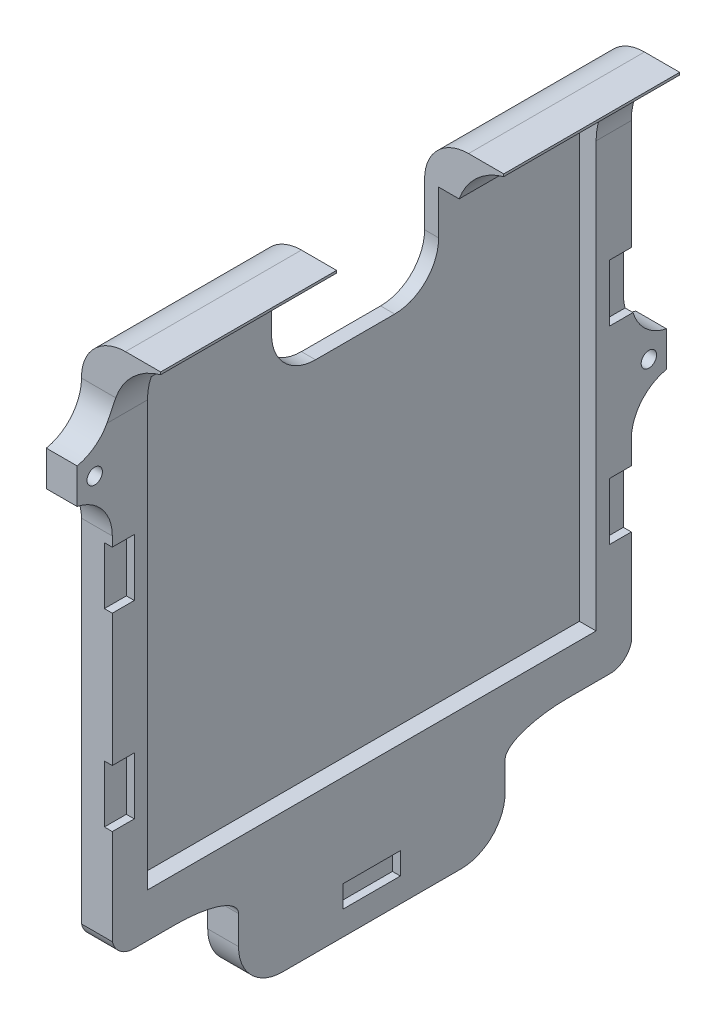
SolidWorks part; units mm, degrees
ref_plane "Front Plane" through (0, 0, 0) normal (0, 0, 1) x (1, 0, 0)
ref_plane "Top Plane" through (0, 0, 0) normal (0, 1, 0) x (1, 0, 0)
ref_plane "Right Plane" through (0, 0, 0) normal (1, 0, 0) x (0, 0, -1)
sketch "Sketch1" plane through (0, 0, 0) normal (0, 0, 1) x (1, 0, 0)
  line L0 (3.4895, 72.6316) -> (3.4895, 65.6316)
  line L1 (-28.7105, -72.8684) -> (-21.7105, -72.8684)
  line L2 (-28.7105, -72.8684) -> (-28.7105, 57.6316)
  line L4 (-21.7105, -72.8684) -> (-21.7105, 50.6316)
  line L5 (-13.7105, 72.6316) -> (3.4895, 72.6316)
  line L6 (-30.2105, 77.6316) -> (-30.2105, 72.6316)
  line L7 (-6.7105, 65.6316) -> (3.4895, 65.6316)
  arc A0 (-28.7105, 57.6316) -> (-13.7105, 72.6316) centre (-13.7105, 57.6316) cw
  arc A1 (-6.7105, 65.6316) -> (-21.7105, 50.6316) centre (-6.7105, 50.6316) ccw
  dimension "D1" = 15
  dimension "D2" = 15
  dimension "D3" = 130.5
  dimension "D4" = 15
  dimension "D5" = 7
  dimension "D6" = 17.2
  dimension "D7" = 7
  dimension "D8" = 8
extrude "Boss-Extrude1" add sketch "Sketch1" along normal blind 118 contours A1 L7 L0 L5 A0 L2 | L1 L4 L2 region at (-22.5509, 9.8219, 0)
sketch "Sketch2" plane through (0, 72.6316, 0) normal (0, 1, 0) x (1, 0, 0)
  line L0 (-13.7105, 0) -> (3.4895, 0) construction
  line L1 (-0.0105, -24) -> (-9.0105, -24)
  line L2 (-0.0105, -24) -> (-0.0105, -39)
  line L3 (-0.0105, -39) -> (-9.0105, -39)
  line L4 (-9.0105, -24) -> (-9.0105, -39)
  line L5 (3.4895, -118) -> (3.4895, 0) construction
  dimension "D1" = 24
  dimension "D2" = 9
  dimension "D3" = 15
  dimension "D4" = 3.5
ref_plane "Plane1" through (0, 0, 59) normal (0, 0, 1) x (1, 0, 0)
extrude "Cut-Extrude2" cut sketch "Sketch2" against normal up to surface (7 mm away) up to face at (-1.6105, 65.6316, 59)
sketch "Sketch5" plane through (-28.7105, 0, 0) normal (-1, 0, 0) x (0, 0, 1)
  line L0 (6, -67.9143) -> (6, 95.8293)
  line L1 (0, -72.8684) -> (0, 50.6316) construction
  line L3 (6, 95.8293) -> (135.0936, 95.8293)
  line L4 (6, 95.8293) -> (6, -67.9143)
  line L5 (6, -67.9143) -> (135.0936, -67.9143)
  line L6 (135.0936, 95.8293) -> (135.0936, -67.9143)
  line M7 (0, -72.8684) -> (118, -72.8684)
  line M8 (118, -72.8684) -> (118, 57.6316)
  line M9 (118, 57.6316) -> (0, 57.6316)
  dimension "D1" = 6
extrude "Cut-Extrude3" [suppressed] cut sketch "Sketch5" against normal blind 98 contours L0 M7 M8 M9 | L6 L3 L0 L5 M9 M8 M7
sketch "Sketch6" plane through (3.4895, 0, 0) normal (1, 0, 0) x (0, 0, -1)
  line L0 (0, 72.6316) -> (0, 65.6316) construction
  line L1 (-21.84, 75.0007) -> (-8.84, 75.0007)
  line L2 (-21.84, 75.0007) -> (-21.84, 67.2604)
  line L3 (-21.84, 67.2604) -> (-8.84, 67.2604)
  line L4 (-8.84, 75.0007) -> (-8.84, 67.2604)
  dimension "D1" = 8.84
  dimension "D2" = 13
extrude "Cut-Extrude4" cut sketch "Sketch6" against normal blind 1.8
sketch "Sketch8" plane through (0, 0, 0) normal (0, 0, -1) x (-1, 0, 0)
  line L0 (21.7105, -72.8684) -> (21.7105, 50.6316) construction
  line L1 (21.7105, 25.6316) -> (23.5105, 25.6316)
  line L2 (21.7105, 25.6316) -> (21.7105, 12.6316)
  line L3 (21.7105, 12.6316) -> (23.5105, 12.6316)
  line L4 (23.5105, 25.6316) -> (23.5105, 12.6316)
  line L5 (13.7105, 72.6316) -> (-3.4895, 72.6316) construction
  line L6 (21.7105, -17.3684) -> (23.5105, -17.3684)
  line L7 (21.7105, -17.3684) -> (21.7105, -30.3684)
  line L8 (21.7105, -30.3684) -> (23.5105, -30.3684)
  line L9 (23.5105, -17.3684) -> (23.5105, -30.3684)
  dimension "D1" = 1.8
  dimension "D2" = 47
  dimension "D3" = 13
  dimension "D4" = 13
  dimension "D5" = 30
  dimension "D6" = 1.8
extrude "Cut-Extrude5" cut sketch "Sketch8" against normal blind 5
mirror "Mirror1" about plane through (0, 0, 59) normal (0, 0, 1) of "Cut-Extrude5"
sketch "Sketch9" plane through (0, 0, 118) normal (0, 0, 1) x (1, 0, 0)
  line L1 (3.4895, 65.6316) -> (-9.5105, 65.6316)
  line L2 (3.4895, 65.6316) -> (3.4895, 67.4316)
  line L3 (3.4895, 67.4316) -> (-9.5105, 67.4316)
  line L4 (-9.5105, 65.6316) -> (-9.5105, 67.4316)
  dimension "D1" = 1.8
  dimension "D2" = 13
extrude "Cut-Extrude6" cut sketch "Sketch9" against normal blind 5
sketch "Sketch11" [suppressed] plane through (-28.7105, 0, 0) normal (-1, 0, 0) x (0, 0, 1)
  line L0 (0, -35.8684) -> (0, -72.3684)
  line L1 (0, -72.3684) -> (39, -72.3684)
  line L2 (118, -72.3684) -> (118, -26.8684)
  line L3 (79, -72.3684) -> (118, -72.3684)
  line L20 (13, -29.8684) -> (8, -29.8684)
  line L21 (5, -26.8684) -> (0, -26.8684)
  line L22 (0, -26.8684) -> (0, -35.8684)
  line L23 (0, -35.8684) -> (14.4398, -35.8684)
  line L24 (31.6067, -45.8684) -> (31.6067, -50.8684)
  line L25 (31.6067, -50.8684) -> (39, -50.8684)
  line L26 (39, -50.8684) -> (39, -62.8684)
  line L27 (44, -67.8684) -> (74, -67.8684)
  line L28 (79, -62.8684) -> (79, -50.8684)
  line L29 (79, -50.8684) -> (86.3933, -50.8684)
  line L30 (86.3933, -50.8684) -> (86.3933, -45.8684)
  line L31 (103.5602, -35.8684) -> (118, -35.8684)
  line L32 (118, -35.8684) -> (118, -26.8684)
  line L33 (118, -26.8684) -> (113, -26.8684)
  line L34 (13, -29.8684) -> (8, -29.8684)
  line L35 (110, -29.8684) -> (62, -29.8684)
  line L36 (57, -24.8684) -> (57, -17.8684)
  line L37 (57, -17.8684) -> (18, -17.8684)
  line L38 (18, -17.8684) -> (18, -24.8684)
  line L39 (110, -29.8684) -> (62, -29.8684)
  line L42 (0, -26.8684) -> (0, -35.8684)
  line L43 (0, -35.8684) -> (14.4398, -35.8684)
  line L44 (31.6067, -45.8684) -> (31.6067, -50.8684)
  line L45 (31.6067, -50.8684) -> (39, -50.8684)
  line L46 (39, -50.8684) -> (39, -72.3684)
  line L48 (79, -72.3684) -> (79, -50.8684)
  line L49 (79, -50.8684) -> (86.3933, -50.8684)
  line L50 (86.3933, -50.8684) -> (86.3933, -45.8684)
  line L51 (103.5602, -35.8684) -> (118, -35.8684)
  line L52 (118, -35.8684) -> (118, -26.8684)
  arc A8 (5, -26.8684) -> (8, -29.8684) centre (8, -26.8684) ccw
  arc A9 (5, -26.8684) -> (8, -29.8684) centre (8, -26.8684) ccw
  arc A10 (110, -29.8684) -> (113, -26.8684) centre (110, -26.8684) ccw
  arc A11 (110, -29.8684) -> (113, -26.8684) centre (110, -26.8684) ccw
  arc A12 (57, -24.8684) -> (62, -29.8684) centre (62, -24.8684) ccw
  arc A13 (57, -24.8684) -> (62, -29.8684) centre (62, -24.8684) ccw
  arc A14 (13, -29.8684) -> (18, -24.8684) centre (13, -24.8684) ccw
  arc A15 (13, -29.8684) -> (18, -24.8684) centre (13, -24.8684) ccw
  arc A24 (74, -67.8684) -> (79, -62.8684) centre (74, -62.8684) ccw
  arc A25 (74, -67.8684) -> (79, -62.8684) centre (74, -62.8684) ccw
  arc A26 (39, -62.8684) -> (44, -67.8684) centre (44, -62.8684) ccw
  arc A27 (39, -62.8684) -> (44, -67.8684) centre (44, -62.8684) ccw
  ellipse E2 centre (14.4398, -45.8684) end of major axis (31.6067, -45.8684) minor radius 10 (31.6067, -45.8684) -> (14.4398, -35.8684) ccw
  ellipse E3 centre (103.5602, -45.8684) end of major axis (86.3933, -45.8684) minor radius 10 (103.5602, -35.8684) -> (86.3933, -45.8684) ccw
  ellipse E4 centre (14.4398, -45.8684) end of major axis (31.6067, -45.8684) minor radius 10 (31.6067, -45.8684) -> (14.4398, -35.8684) ccw
  ellipse E5 centre (103.5602, -45.8684) end of major axis (86.3933, -45.8684) minor radius 10 (103.5602, -35.8684) -> (86.3933, -45.8684) ccw
  dimension "D1" = 0
sketch "Sketch14" plane through (-21.7105, 0, 0) normal (1, 0, 0) x (0, 0, -1)
  line L12 (-85.5934, -0.8635) -> (-45.5934, -0.8635)
  line L13 (-83.0934, 1.6365) -> (-48.0934, 1.6365)
  line L15 (-83.0934, 1.6365) -> (-83.0934, 51.6365)
  line L17 (-48.0934, 1.6365) -> (-48.0934, 51.6365)
  line L18 (-45.5934, -0.8635) -> (-45.5934, 51.6365)
  line L20 (-85.5934, -0.8635) -> (-85.5934, 51.6365)
  line L21 (-85.5934, 51.6365) -> (-83.0934, 51.6365)
  line L23 (-85.5934, -0.8635) -> (-85.5934, 54.1365) construction
  line L24 (-85.5934, 54.1365) -> (-45.5934, 54.1365) construction
  line L25 (-45.5934, -0.8635) -> (-45.5934, 54.1365) construction
  line L26 (-83.0934, 51.6365) -> (-48.0934, 51.6365) construction
  line L27 (-48.0934, 51.6365) -> (-45.5934, 51.6365)
  dimension "D1" = 2.5
  dimension "D2" = 35
  dimension "D3" = 50
extrude "Boss-Extrude3" [suppressed] add sketch "Sketch14" along normal blind 10
sketch "Sketch15" plane through (3.4895, 0, 0) normal (1, 0, 0) x (0, 0, -1)
  line L0 (-113, 65.6316) -> (0, 65.6316) construction
  line L1 (-118, 65.6316) -> (0, 65.6316)
  line L2 (-118, 65.6316) -> (-118, 72.6316)
  line L3 (-118, 72.6316) -> (0, 72.6316)
  line L4 (0, 65.6316) -> (0, 72.6316)
  dimension "D1" = 0
extrude "Cut-Extrude7" cut sketch "Sketch15" against normal blind 57
sketch "Sketch24" plane through (-28.7105, 0, 0) normal (-1, 0, 0) x (0, 0, 1)
  line L0 (5, -44.8684) -> (5, 52.9406)
  line L1 (5, 52.9406) -> (0, 52.9406)
  line L2 (0, 52.9406) -> (0, -52.0594)
  line L3 (31.6067, -72.8684) -> (31.6067, -67.8684)
  line L4 (28.6941, -60.8684) -> (28.6941, -67.8684)
  line L5 (31.6067, -67.8684) -> (31.6067, -60.8684)
  line L6 (5, -55.8684) -> (14.4398, -55.8684)
  line L7 (14.4398, -50.8684) -> (11, -50.8684)
  line L8 (0, -72.8684) -> (0, 57.6316) construction
  line L9 (118, -72.8684) -> (0, -72.8684) construction
  line L47 (59, 91.3004) -> (59, -88.244) construction
  line L48 (59, -17.71) -> (59, 17.71) construction
  line L49 (103.5602, -50.8684) -> (107, -50.8684)
  line L50 (113, -55.8684) -> (103.5602, -55.8684)
  line L51 (86.3933, -67.8684) -> (86.3933, -60.8684)
  line L52 (89.3059, -60.8684) -> (89.3059, -67.8684)
  line L53 (86.3933, -72.8684) -> (86.3933, -67.8684)
  line L54 (118, 52.9406) -> (118, -52.0594)
  line L55 (113, 52.9406) -> (118, 52.9406)
  line L56 (113, -44.8684) -> (113, 52.9406)
  line L57 (31.6067, -72.8684) -> (86.3933, -72.8684)
  line L58 (0, -52.0594) -> (0, -72.8684)
  line L59 (0, -72.8684) -> (31.6067, -72.8684)
  line L60 (86.3933, -72.8684) -> (118, -72.8684)
  line L61 (118, -72.8684) -> (118, -52.0594)
  arc A0 (5, -44.8684) -> (11, -50.8684) centre (11, -44.8684) ccw
  arc A1 (0, -52.0594) -> (5, -55.8684) centre (4.8566, -50.8705) ccw
  arc A8 (118, -52.0594) -> (113, -55.8684) centre (113.1434, -50.8705) cw
  arc A9 (113, -44.8684) -> (107, -50.8684) centre (107, -44.8684) cw
  ellipse E0 centre (31.6067, -67.8684) end of major axis (31.6067, -62.8684) minor radius 2.9126 (28.6941, -67.8684) -> (31.6067, -72.8684) ccw
  ellipse E1 centre (14.4398, -60.8684) end of major axis (28.6941, -60.8684) minor radius 5 (28.6941, -60.8684) -> (14.4398, -55.8684) ccw
  ellipse E2 centre (14.4398, -60.8684) end of major axis (31.6067, -60.8684) minor radius 10 (31.6067, -60.8684) -> (14.4398, -50.8684) ccw
  ellipse E3 centre (103.5602, -60.8684) end of major axis (86.3933, -60.8684) minor radius 10 (86.3933, -60.8684) -> (103.5602, -50.8684) cw
  ellipse E4 centre (103.5602, -60.8684) end of major axis (117.8144, -60.8684) minor radius 5 (89.3059, -60.8684) -> (103.5602, -55.8684) cw
  ellipse E5 centre (86.3933, -67.8684) end of major axis (86.3933, -62.8684) minor radius 2.9126 (89.3059, -67.8684) -> (86.3933, -72.8684) cw
  line M56 (0, 57.6316) -> (0, -72.8684)
  line M57 (0, -72.8684) -> (118, -72.8684)
  line M58 (118, -72.8684) -> (118, 57.6316)
  dimension "D1" = 0
  dimension "D2" = 0
extrude "Cut-Extrude8" cut sketch "Sketch24" against normal blind 57 contours L4 E1 L6 A1 E0 M56 M57 | L52 E5 A8 L50 E4 M57 M58 region at (-28.7105, -64.5576, 104.0418) region at (-28.7105, -64.5576, 13.9582)
fillet "Fillet1" radius 10 1 edges at (-26.3991, 65.6316, 59)
sketch "Sketch26" plane through (-28.7105, 0, 0) normal (-1, 0, 0) x (0, 0, 1)
  line L0 (0, -52.0594) -> (0, 55.6316) construction
  line L1 (0, 5.6316) -> (-8, 5.6316)
  line L2 (0, 5.6316) -> (0, -2.3684)
  line L3 (0, -2.3684) -> (-8, -2.3684)
  line L4 (-8, 5.6316) -> (-8, -2.3684)
  line L5 (118, -52.0594) -> (118, 55.6316) construction
  line L6 (118, 45.6316) -> (126, 45.6316)
  line L7 (118, 45.6316) -> (118, 37.6316)
  line L8 (118, 37.6316) -> (126, 37.6316)
  line L9 (126, 45.6316) -> (126, 37.6316)
  line L10 (0, 65.6316) -> (118, 65.6316) construction
  circle A0 centre (122, 41.6316) radius 1.75
  circle A1 centre (-4, 1.6316) radius 1.75
  dimension "D7" = 3.5
  dimension "D8" = 4
  dimension "D9" = 4
  dimension "D10" = 4
  dimension "D11" = 4
  dimension "D12" = 3.5
  dimension "D1" = 8
  dimension "D2" = 8
  dimension "D3" = 8
  dimension "D4" = 8
  dimension "D5" = 60
  dimension "D6" = 20
extrude "Boss-Extrude4" add sketch "Sketch26" against normal up to surface (7 mm away) contours L7 L6 L9 L8 | A0 | L2 L1 L4 L3 | A1 up to face at (-21.7105, -22.3067, 59)
fillet "Fillet2" radius 10 4 edges at (-25.2105, 37.6316, 118) (-25.2105, 45.6316, 118) (-25.2105, -2.3684, 0) (-25.2105, 5.6316, 0)
sketch "Sketch27" plane through (0, 65.6316, 0) normal (0, 1, 0) x (1, 0, 0)
  line L0 (-6.7105, -118) -> (-6.7105, 0) construction
  line L1 (-6.7105, -40) -> (-30.2905, -40)
  line L2 (-6.7105, -40) -> (-6.7105, -78)
  line L3 (-6.7105, -78) -> (-30.2905, -78)
  line L4 (-30.2905, -40) -> (-30.2905, -78)
  line L5 (-18.7105, 0) -> (-6.7105, 0) construction
  line L6 (-18.7105, -118) -> (-6.7105, -118) construction
  dimension "D1" = 40
  dimension "D2" = 40
extrude "Cut-Extrude10" cut sketch "Sketch27" against normal blind 30
fillet "Fillet3" radius 10 2 edges at (-25.2105, 35.6316, 78) (-25.2105, 35.6316, 40)
sketch "Sketch28" plane through (3.4895, 0, 0) normal (1, 0, 0) x (0, 0, -1)
  line L0 (-5, -55.8684) -> (-14.4398, -55.8684) construction
  line L1 (-110, 55.6316) -> (-8, 55.6316)
  line L2 (-110, 55.6316) -> (-110, -45.8684)
  line L3 (-110, -45.8684) -> (-8, -45.8684)
  line L4 (-8, 55.6316) -> (-8, -45.8684)
  line L5 (-39, 65.6316) -> (-24, 65.6316) construction
  line L6 (0, 15.4295) -> (0, 25.6316) construction
  line L7 (-118, 12.6316) -> (-118, 25.6316) construction
  dimension "D1" = 10
  dimension "D2" = 10
  dimension "D3" = 8
  dimension "D4" = 8
extrude "Cut-Extrude11" cut sketch "Sketch28" against normal blind 29
sketch "Sketch29" plane through (0, -72.8684, 0) normal (0, -1, 0) x (1, 0, 0)
  line L0 (-21.7105, 14.4398) -> (-21.7105, 28.6941) construction
  line L1 (-28.7105, 89.3059) -> (-21.7105, 89.3059)
  line L2 (-28.7105, 89.3059) -> (-28.7105, 28.6941)
  line L3 (-28.7105, 28.6941) -> (-21.7105, 28.6941)
  line L4 (-21.7105, 89.3059) -> (-21.7105, 28.6941)
extrude "Boss-Extrude5" add sketch "Sketch29" along normal blind 4.5 and the other way blind 5
sketch "Sketch30" plane through (0, 65.6316, 0) normal (0, 1, 0) x (1, 0, 0)
  line L0 (-18.7105, -118) -> (-6.7105, -118) construction
  line L1 (-6.7105, 0) -> (-10.7105, 0)
  line L2 (-6.7105, 0) -> (-6.7105, -118)
  line L3 (-6.7105, -118) -> (-10.7105, -118)
  line L4 (-10.7105, 0) -> (-10.7105, -118)
  dimension "D1" = 4
extrude "Cut-Extrude12" cut sketch "Sketch30" against normal blind 5
sketch "Sketch25" plane through (-21.7105, 0, 0) normal (1, 0, 0) x (0, 0, -1)
  line L0 (-86.3933, -72.8684) -> (-31.6067, -72.8684) construction
  line L1 (-65.4991, -71.8684) -> (-52.4991, -71.8684)
  line L2 (-65.4991, -71.8684) -> (-65.4991, -66.8684)
  line L3 (-65.4991, -66.8684) -> (-52.4991, -66.8684)
  line L4 (-52.4991, -71.8684) -> (-52.4991, -66.8684)
  line L5 (-28.6941, -60.8684) -> (-28.6941, -77.3684) construction
  line L6 (-89.3059, -60.8684) -> (-89.3059, -77.3684) construction
  dimension "D1" = 1
  dimension "D2" = 13
  dimension "D3" = 5
  dimension "D4" = 23.805
  dimension "D5" = 23.8069
extrude "Cut-Extrude9" cut sketch "Sketch25" against normal blind 1.8
fillet "Fillet4" radius 10 2 edges at (-25.2105, -77.3684, 89.3059) (-25.2105, -77.3684, 28.6941)
